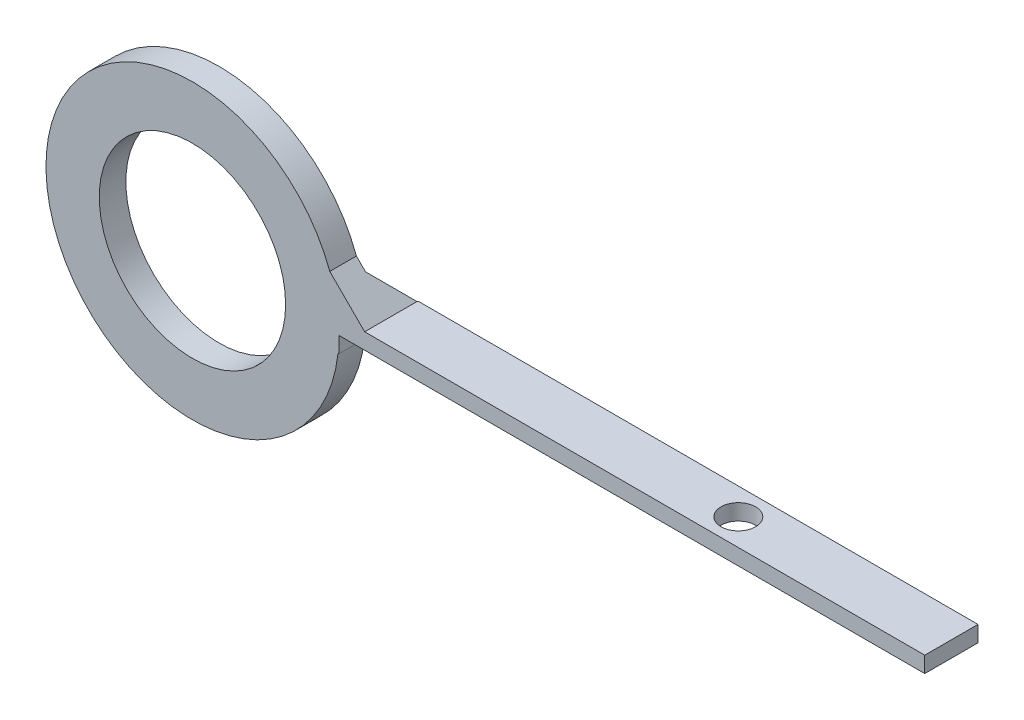
SolidWorks part; units mm, degrees
ref_plane "Front Plane" through (0, 0, 0) normal (0, 0, 1) x (1, 0, 0)
ref_plane "Top Plane" through (0, 0, 0) normal (0, 1, 0) x (1, 0, 0)
ref_plane "Right Plane" through (0, 0, 0) normal (1, 0, 0) x (0, 0, -1)
sketch "Sketch1" plane through (0, 0, 0) normal (0, 0, 1) x (1, 0, 0)
  circle A0 centre (0, 0) radius 27.5
  circle A1 centre (0, 0) radius 17.5
  dimension "D1" = 35
  dimension "D2" = 10
extrude "Boss-Extrude1" add sketch "Sketch1" along normal blind 5
sketch "Sketch2" plane through (0, 0, 5) normal (0, 0, 1) x (1, 0, 0)
  line L1 (17.5, 3) -> (137.5, 3)
  line L2 (17.5, 3) -> (17.5, -3)
  line L3 (17.5, -3) -> (137.5, -3)
  line L4 (137.5, 3) -> (137.5, -3)
  circle A0 centre (0, 0) radius 17.5 construction
  dimension "D1" = 3
  dimension "D2" = 3
  dimension "D3" = 17.5
  dimension "D4" = 120
extrude "Boss-Extrude2" add sketch "Sketch2" against normal blind 10
sketch "Sketch3" plane through (17.5, 0, 0) normal (-1, 0, 0) x (0, 0, 1)
  line L1 (-5, -3) -> (0, -3)
  line L2 (-5, -3) -> (-5, 0)
  line L3 (-5, 0) -> (0, 0)
  line L4 (0, -3) -> (0, 0)
extrude "Cut-Extrude2" cut sketch "Sketch3" against normal blind 140
sketch "Sketch4" plane through (17.5, 0, 0) normal (-1, 0, 0) x (0, 0, 1)
  line L1 (-5, 3) -> (0, 3)
  line L2 (-5, 3) -> (-5, 0)
  line L3 (-5, 0) -> (0, 0)
  line L4 (0, 3) -> (0, 0)
extrude "Cut-Extrude3" cut sketch "Sketch4" against normal blind 10
chamfer "Chamfer2" distance 5 angle 45 1 edges at (27.5, 1.5, -5)
sketch "Sketch5" plane through (137.5, 0, 0) normal (1, 0, 0) x (0, 0, -1)
  line L0 (-5, -3) -> (-5, 3) construction
  line L1 (0, -3) -> (-5, -3)
  line L2 (0, -3) -> (0, 0)
  line L3 (0, 0) -> (-5, 0)
  line L4 (-5, -3) -> (-5, 0)
extrude "Cut-Extrude4" cut sketch "Sketch5" against normal blind 110
chamfer "Chamfer3" distance 5 angle 45 1 edges at (27.3359, 3, 2.5) first distance on face at (64.9453, 3, 0)
sketch "Sketch6" plane through (0, 0, 0) normal (0, -1, 0) x (1, 0, 0)
  line L0 (137.5, -5) -> (137.5, 5) construction
  circle A0 centre (97.5, 0) radius 3.25
  point P4 (137.5, 0)
  dimension "D1" = 6.5
  dimension "D2" = 40
extrude "Cut-Extrude5" cut sketch "Sketch6" against normal blind 110
